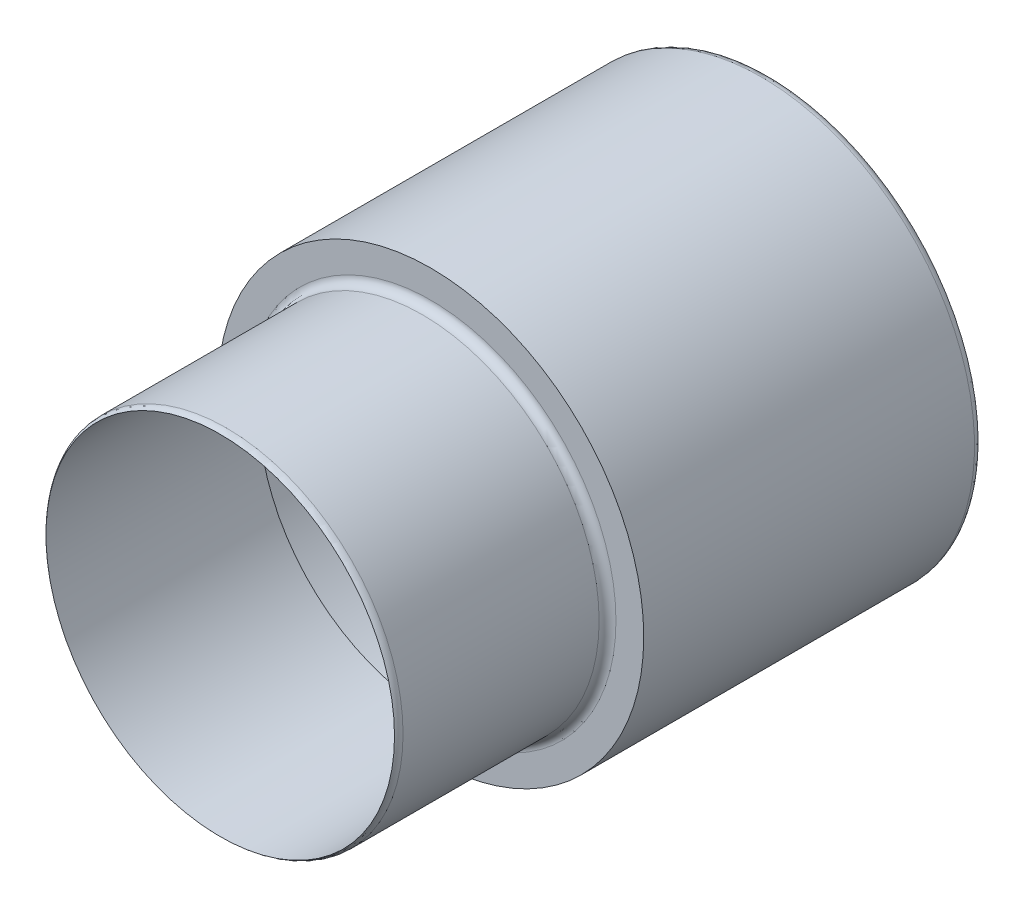
SolidWorks part; units mm, degrees
ref_plane "Front" through (0, 0, 0) normal (0, 0, 1) x (1, 0, 0)
ref_plane "Top" through (0, 0, 0) normal (0, 1, 0) x (1, 0, 0)
ref_plane "Right" through (0, 0, 0) normal (1, 0, 0) x (0, 0, -1)
sketch "Sketch1" plane through (0, 0, 0) normal (0, 0, 1) x (1, 0, 0)
  circle A0 centre (0, 0) radius 253
  dimension "D1" = 506
extrude "Boss-Extrude1" add sketch "Sketch1" along normal blind 400
sketch "Sketch2" plane through (0, 0, 400) normal (0, 0, 1) x (1, 0, 0)
  circle A0 centre (0, 0) radius 210
  dimension "D1" = 420
extrude "Boss-Extrude2" add sketch "Sketch2" along normal blind 250
shell "Shell1" thickness 3 removed face at (253, 0, 0) removed face at (210, 0, 650)
fillet "Fillet1" radius 10 3 edges at (210, 0, 400) (210, 0, 650) (253, 0, 0)
